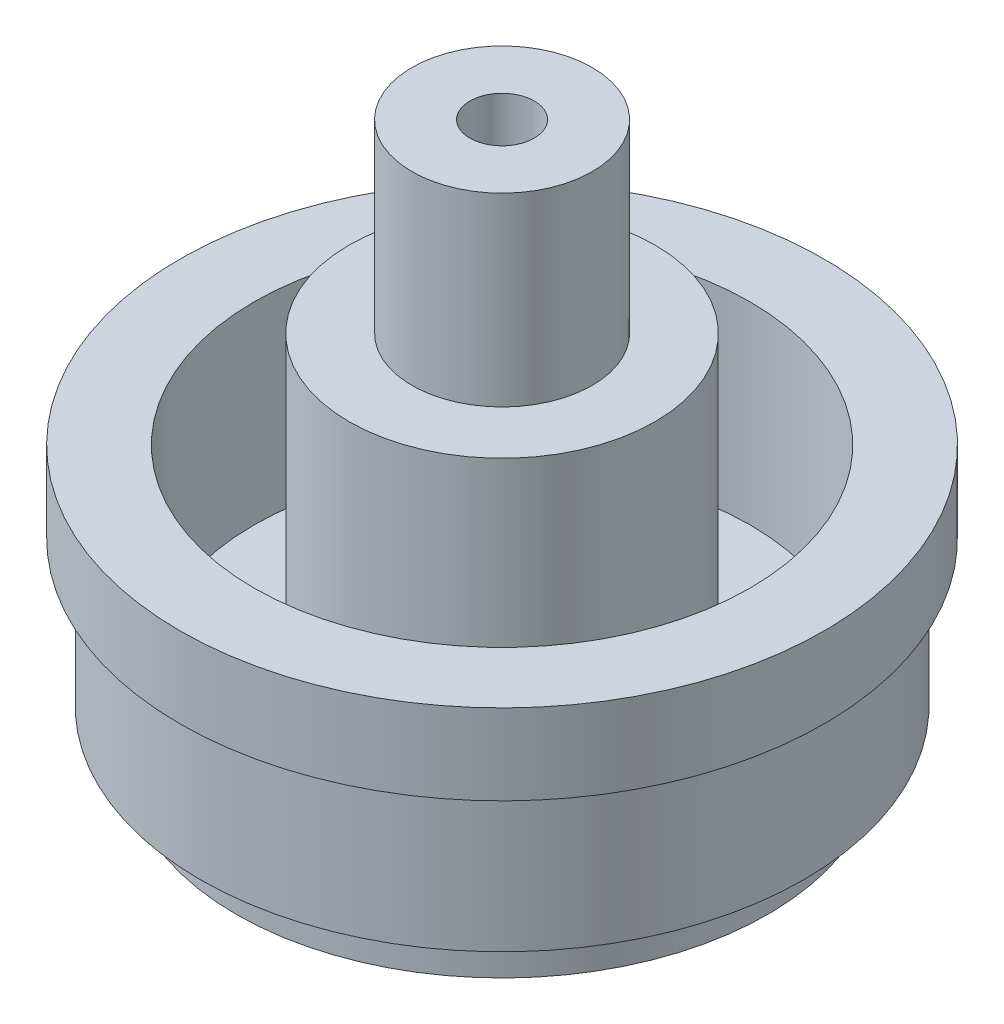
SolidWorks part; units mm, degrees
ref_plane "Front Plane" through (0, 0, 0) normal (0, 0, 1) x (1, 0, 0)
ref_plane "Top Plane" through (0, 0, 0) normal (0, 1, 0) x (1, 0, 0)
ref_plane "Right Plane" through (0, 0, 0) normal (1, 0, 0) x (0, 0, -1)
sketch "Sketch1" plane through (0, 0, 0) normal (0, 1, 0) x (1, 0, 0)
  circle A0 centre (0, 0) radius 50.8
  circle A1 centre (0, 0) radius 39.116
  dimension "D1" = 101.6
  dimension "D2" = 78.232
extrude "Boss-Extrude1" add sketch "Sketch1" against normal blind 12.7
ref_plane "Plane4" through (0, -15.24, 0) normal (0, -1, 0) x (-1, 0, 0)
sketch "Sketch2" plane through (0, -15.24, 0) normal (0, -1, 0) x (-1, 0, 0)
  circle A0 centre (0, 0) radius 47.625
  circle A1 centre (0, 0) radius 39.116
  dimension "D1" = 95.25
  dimension "D2" = 78.232
extrude "Boss-Extrude2" add sketch "Sketch2" against normal up to surface (2.54 mm away) and the other way blind 20.32 separate body up to face at (0, -12.7, 39.116)
ref_plane "Plane5" through (0, -38.1, 0) normal (0, 1, 0) x (1, 0, 0)
sketch "Sketch4" plane through (0, -38.1, 0) normal (0, 1, 0) x (1, 0, 0)
  circle A0 centre (0, 0) radius 41.91
  dimension "D1" = 83.82
extrude "Boss-Extrude3" add sketch "Sketch4" along normal offset from surface 30.48 and the other way blind 5.08 up to face at (0, 0, 39.116)
ref_plane "Plane6" through (0, -27.94, 0) normal (0, 1, 0) x (1, 0, 0)
sketch "Sketch5" plane through (0, -27.94, 0) normal (0, 1, 0) x (1, 0, 0)
  circle A0 centre (0, 0) radius 24.13
  dimension "D1" = 48.26
extrude "Boss-Extrude4" add sketch "Sketch5" along normal blind 45.72 from surface starting at face at (0, -30.48, 39.116)
ref_plane "Plane7" through (0, 17.78, 0) normal (0, 1, 0) x (1, 0, 0)
sketch "Sketch6" plane through (0, 17.78, 0) normal (0, 1, 0) x (1, 0, 0)
  circle A0 centre (0, 0) radius 14.224
  dimension "D1" = 28.448
extrude "Boss-Extrude5" add sketch "Sketch6" along normal blind 29.21 from surface starting at face at (0, 15.24, 24.13)
ref_plane "Plane8" through (0, -45.72, 0) normal (0, -1, 0) x (-1, 0, 0)
sketch "Sketch7" plane through (0, -45.72, 0) normal (0, -1, 0) x (-1, 0, 0)
  circle A0 centre (0, 0) radius 16.51
  dimension "D1" = 33.02
extrude "Cut-Extrude1" cut sketch "Sketch7" against normal blind 50.8
ref_plane "Plane9" through (0, 46.99, 0) normal (0, 1, 0) x (1, 0, 0)
sketch "Sketch8" plane through (0, 46.99, 0) normal (0, 1, 0) x (1, 0, 0)
  circle A0 centre (0, 0) radius 5.08
  dimension "D1" = 10.16
extrude "Cut-Extrude2" cut sketch "Sketch8" against normal blind 26.416
